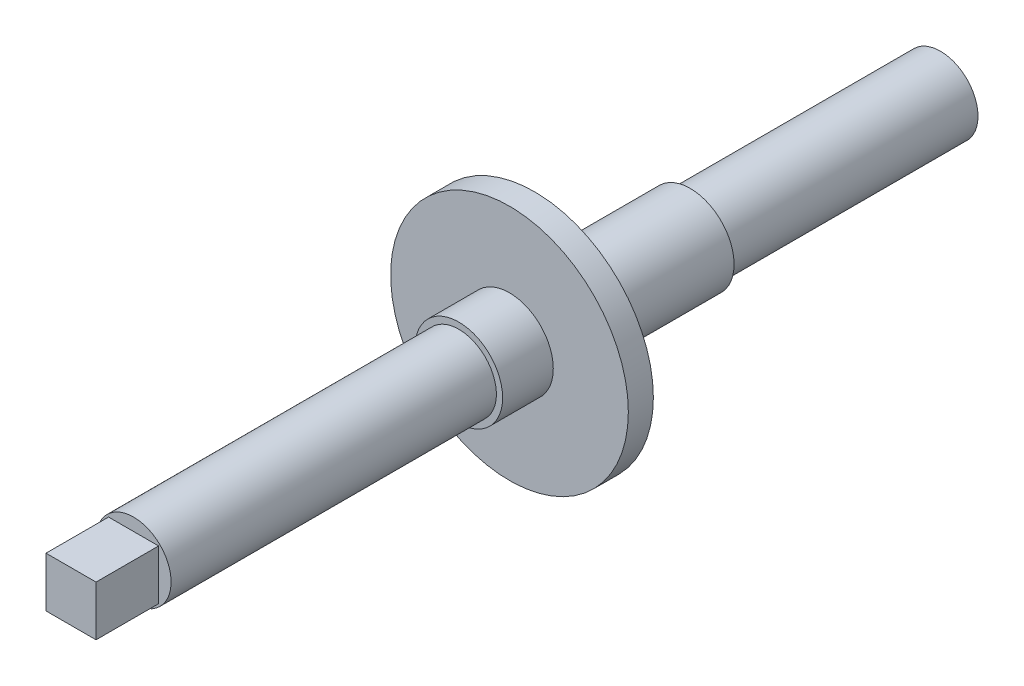
SolidWorks part; units mm, degrees
ref_plane "Alzado" through (0, 0, 0) normal (0, 0, 1) x (1, 0, 0)
ref_plane "Planta" through (0, 0, 0) normal (0, 1, 0) x (1, 0, 0)
ref_plane "Vista lateral" through (0, 0, 0) normal (1, 0, 0) x (0, 0, -1)
sketch "Croquis1" plane through (0, 0, 0) normal (0, 0, 1) x (1, 0, 0)
  circle A0 centre (0, 0) radius 3
extrude "Saliente-Extruir1" add sketch "Croquis1" along normal blind 20
sketch "Croquis2" plane through (0, 0, 20) normal (0, 0, 1) x (1, 0, 0)
  circle A0 centre (0, 0) radius 3.5
extrude "Saliente-Extruir2" add sketch "Croquis2" along normal blind 12.45
sketch "Croquis3" plane through (0, 0, 32.45) normal (0, 0, 1) x (1, 0, 0)
  circle A0 centre (0, 0) radius 9.5
extrude "Saliente-Extruir3" add sketch "Croquis3" along normal blind 2
sketch "Croquis4" plane through (0, 0, 34.45) normal (0, 0, 1) x (1, 0, 0)
  circle A0 centre (0, 0) radius 3.5
extrude "Saliente-Extruir4" add sketch "Croquis4" along normal blind 4.05
sketch "Croquis5" plane through (0, 0, 38.5) normal (0, 0, 1) x (1, 0, 0)
  circle A0 centre (0, 0) radius 3
extrude "Saliente-Extruir5" add sketch "Croquis5" along normal blind 26
sketch "Croquis6" plane through (0, 0, 64.5) normal (0, 0, 1) x (1, 0, 0)
  line L1 (-2, -2) -> (2, -2)
  line L2 (-2, -2) -> (-2, 2)
  line L3 (-2, 2) -> (2, 2)
  line L4 (2, -2) -> (2, 2)
  line L5 (-2, -2) -> (2, 2) construction
  line L6 (-2, 2) -> (2, -2) construction
  point P0 (0, 0)
  dimension "D1" = 4
  dimension "D2" = 4
extrude "Saliente-Extruir6" add sketch "Croquis6" along normal blind 5
